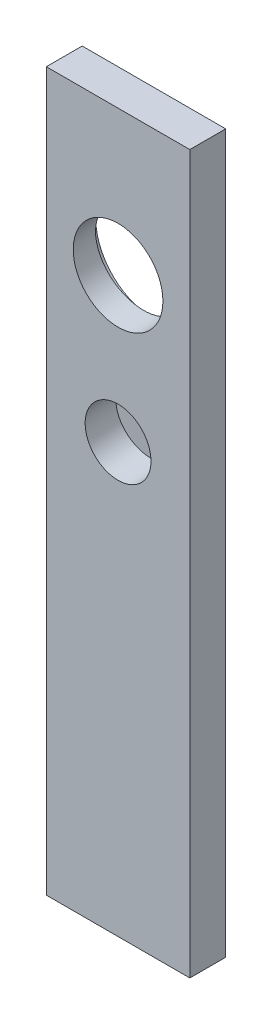
SolidWorks part; units mm, degrees
ref_plane "Front Plane" through (0, 0, 0) normal (0, 0, 1) x (1, 0, 0)
ref_plane "Top Plane" through (0, 0, 0) normal (0, 1, 0) x (1, 0, 0)
ref_plane "Right Plane" through (0, 0, 0) normal (1, 0, 0) x (0, 0, -1)
sketch "Sketch1" plane through (0, 0, 0) normal (0, 0, 1) x (1, 0, 0)
  line L1 (-40, 200) -> (40, 200)
  line L2 (-40, 200) -> (-40, -200)
  line L3 (-40, -200) -> (40, -200)
  line L4 (40, 200) -> (40, -200)
  line L5 (-40, 200) -> (40, -200) construction
  line L6 (-40, -200) -> (40, 200) construction
  point P0 (0, 0)
  dimension "D1" = 400
  dimension "D2" = 80
extrude "Boss-Extrude1" add sketch "Sketch1" along normal blind 20
sketch "Sketch2" plane through (0, 0, 20) normal (0, 0, 1) x (1, 0, 0)
  line L0 (0, -200) -> (0, 120)
  line L1 (-40, -200) -> (40, -200) construction
  dimension "D1" = 320
ref_plane "Plane1" through (0, 120, 0) normal (0, 1, 0) x (1, 0, 0)
sketch "Sketch3" plane through (0, 120, 0) normal (0, 1, 0) x (1, 0, 0)
  line L0 (0, -20) -> (0, 0)
  line L2 (0, -7.5) -> (15.3391, -7.5) construction
ref_plane "Plane3" through (0, 0.062, -0.8869) normal (0, 0.0698, -0.9976) x (1, 0, 0)
sketch "Sketch4" plane through (0, 0.062, -0.8869) normal (0, 0.0698, -0.9976) x (1, 0, 0)
  line L0 (0, -121.1028) -> (0, -119.7077) construction
  circle A0 centre (0, -120.4053) radius 32.5
  dimension "D1" = 65
extrude "Cut-Extrude4" cut sketch "Sketch4" along normal through all
sketch "Sketch6" plane through (0, 0.062, -0.8869) normal (0, 0.0698, -0.9976) x (-1, 0, 0)
  circle A1 centre (0, 120.4053) radius 25
  dimension "D1" = 50
extrude "Cut-Extrude6" cut sketch "Sketch6" against normal through all
ref_axis "Axis1" through (-44, 0, 0) along (1, 0, 0)
ref_plane "Plane5" through (0, 0, 0) normal (0, -0.0698, 0.9976) x (1, 0, 0)
sketch "Sketch12" plane through (0, 0, 0) normal (0, -0.0698, 0.9976) x (1, 0, 0)
  line L0 (0, -11) -> (0, 11) construction
  circle A0 centre (0, 40) radius 18.35
  dimension "D1" = 36.7
  dimension "D2" = 40
extrude "Cut-Extrude8" cut sketch "Sketch12" along normal through all
sketch "Sketch13" plane through (0, 0, 0) normal (0, -0.0698, 0.9976) x (1, 0, 0)
  line L0 (0, -11) -> (0, 11) construction
  circle A0 centre (0, 46.65) radius 6
  circle A1 centre (0, 40) radius 18.35 construction
  dimension "D1" = 12
  dimension "D2" = 6.65
extrude "Cut-Extrude9" cut sketch "Sketch13" against normal through all
